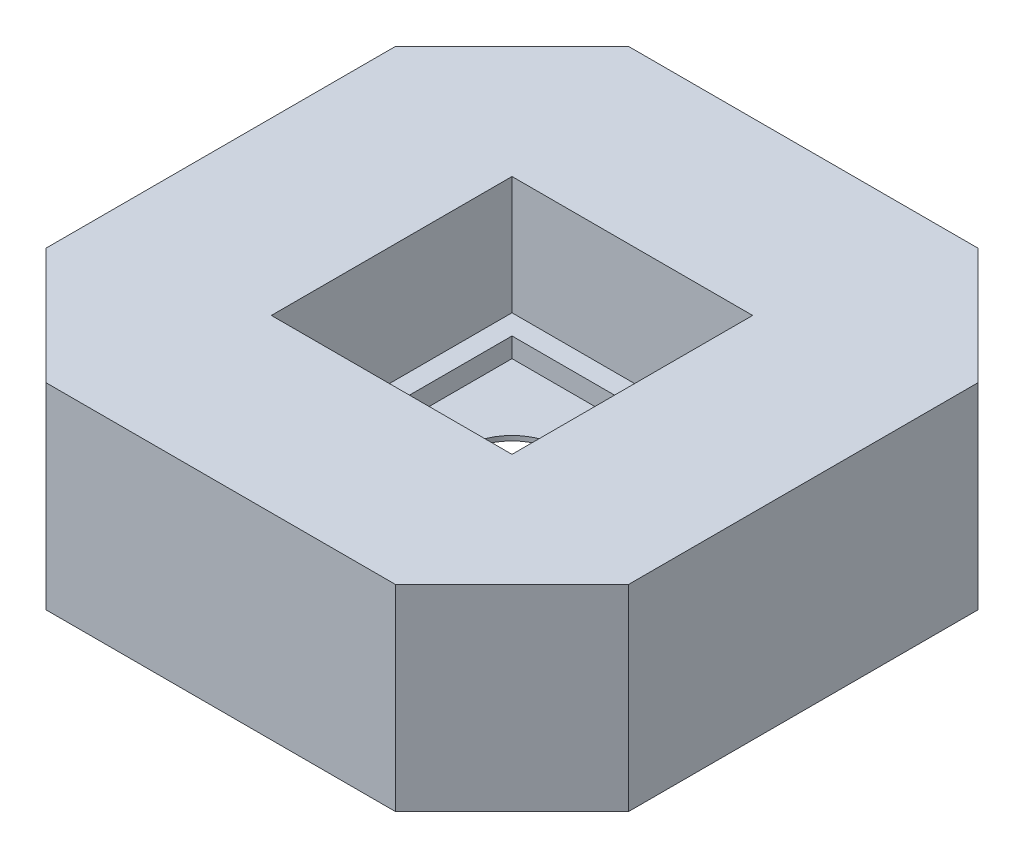
SolidWorks part; units mm, degrees
ref_plane "前视基准面" through (0, 0, 0) normal (0, 0, 1) x (1, 0, 0)
ref_plane "上视基准面" through (0, 0, 0) normal (0, 1, 0) x (1, 0, 0)
ref_plane "右视基准面" through (0, 0, 0) normal (1, 0, 0) x (0, 0, -1)
other "Configuration Table"
sketch "草图1" plane through (0, 0, 0) normal (0, 1, 0) x (1, 0, 0)
  line L0 (-305, 183) -> (-183, 305)
  line L1 (-183, 305) -> (183, 305)
  line L2 (-305, 183) -> (-305, -183)
  line L3 (-183, -305) -> (183, -305)
  line L4 (305, 183) -> (305, -183)
  line L5 (-305, 305) -> (305, -305) construction
  line L6 (-305, -305) -> (305, 305) construction
  line L7 (-305, -183) -> (-183, -305)
  line L8 (183, 305) -> (305, 183)
  line L9 (305, -183) -> (183, -305)
  point P0 (0, 0)
  dimension "D1" = 610
extrude "凸台-拉伸1" add sketch "草图1" along normal blind 206
sketch "草图4" plane through (0, 206, 0) normal (0, 1, 0) x (1, 0, 0)
  line L1 (-126, 126) -> (126, 126)
  line L2 (-126, 126) -> (-126, -126)
  line L3 (-126, -126) -> (126, -126)
  line L4 (126, 126) -> (126, -126)
  line L5 (-126, 126) -> (126, -126) construction
  line L6 (-126, -126) -> (126, 126) construction
  point P0 (0, 0)
  dimension "D1" = 252
extrude "切除-拉伸3" cut sketch "草图4" against normal blind 123.6
sketch "草图5" plane through (0, 206, 0) normal (0, 1, 0) x (1, 0, 0)
  line L1 (-105, 105) -> (105, 105)
  line L2 (-105, 105) -> (-105, -105)
  line L3 (-105, -105) -> (105, -105)
  line L4 (105, 105) -> (105, -105)
  line L5 (-105, 105) -> (105, -105) construction
  line L6 (-105, -105) -> (105, 105) construction
  point P0 (0, 0)
  dimension "D1" = 210
extrude "切除-拉伸5" cut sketch "草图5" against normal blind 144.2
shell "抽壳10" thickness 5 removed face at (0, 0, 0)
sketch "草图6" plane through (0, 61.8, 0) normal (0, 1, 0) x (1, 0, 0)
  circle A0 centre (0, 0) radius 50
  dimension "D1" = 100
extrude "切除-拉伸6" cut sketch "草图6" against normal through all
ref_plane "基准面2" through (91.5, 0, 0) normal (1, 0, 0) x (0, 0, -1)
sketch "草图11" plane through (91.5, 0, 0) normal (1, 0, 0) x (0, 0, -1)
  line L0 (-131, 82.4) -> (-300, 112.1993)
  line L1 (-131, 77.4) -> (-131, 201) construction
  line L2 (-300, 201) -> (-300, 0) construction
  line L3 (131, 77.4) -> (-131, 77.4) construction
  dimension "D1" = 80
  dimension "D2" = 5
rib "筋2" sketch "草图11" sketch "草图11" thickness 10 extrusion direction parallel to sketch draft on no parameters "D1"=10
mirror "镜向1" about plane through (0, 0, 0) normal (1, 0, 0) of "筋2"
pattern_circular "阵列(圆周)1" count 4 over 360 about axis through (0, 56.8, 0) along (0, 1, 0) of "镜向1"
